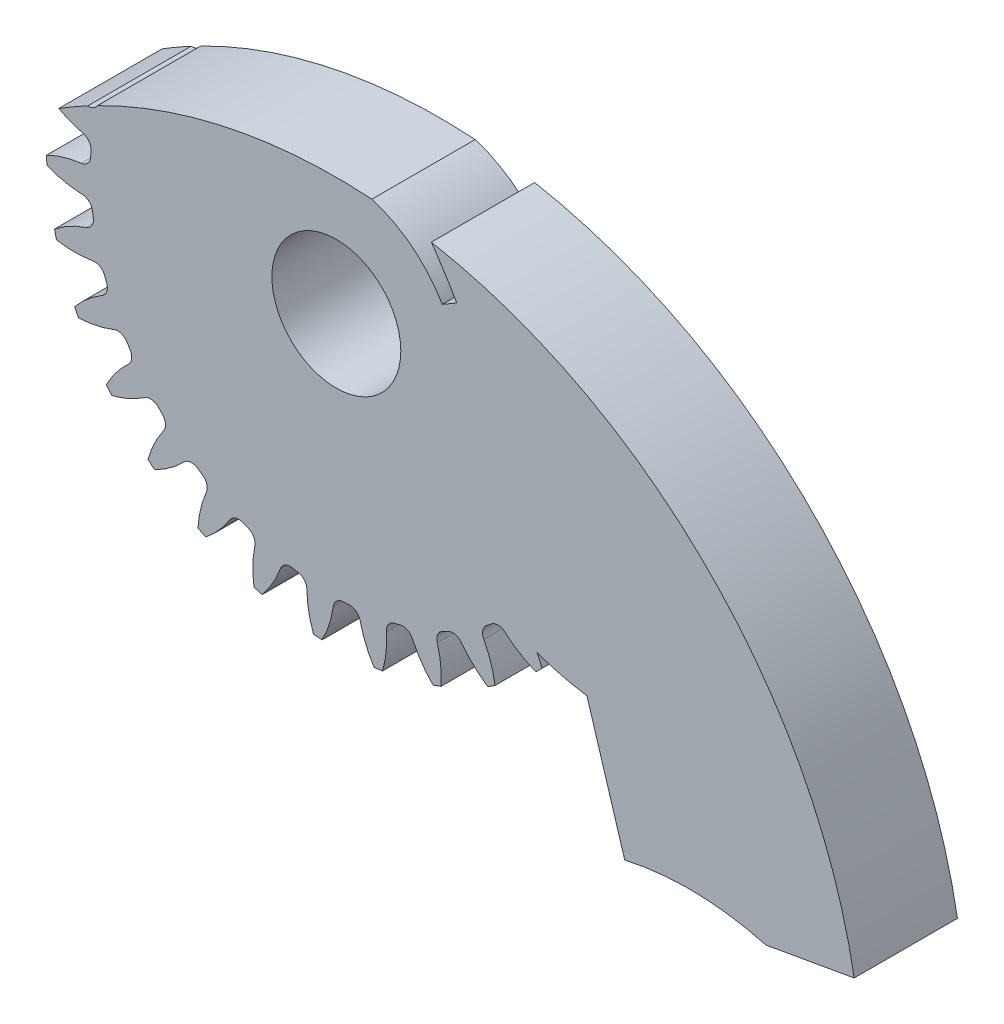
SolidWorks part; units mm, degrees
material "ABS"
ref_plane "Front" through (0, 0, 0) normal (0, 0, 1) x (1, 0, 0)
ref_plane "Top" through (0, 0, 0) normal (0, 1, 0) x (1, 0, 0)
ref_plane "Right" through (0, 0, 0) normal (1, 0, 0) x (0, 0, -1)
sketch "Sketch3" plane through (0, 0, 0) normal (0, 0, 1) x (1, 0, 0)
  circle A0 centre (0, 0) radius 40.64
  dimension "od" = 81.28
extrude "gearBody" add sketch "Sketch3" along normal blind 9.652
sketch "Sketch2" plane through (0, 0, 0) normal (0, 0, 1) x (1, 0, 0)
  line L0 (0, 0) -> (34.0786, 14.1158) construction
  line L1 (45.4751, -11.4855) -> (0, 0) construction
  line L2 (0, 0) -> (36.3143, 0) construction
  line L3 (38.0972, -0.458) -> (37.8451, -4.4001) construction
  line L5 (37.9712, -2.4291) -> (0, 0) construction
  line L7 (0, 0) -> (36.8864, 0) construction
  arc A0 (36.879, -0.7403) -> (36.6727, -3.9649) centre (0, 0) ccw construction
  arc A1 (40.637, 0.4947) -> (40.2427, -5.6687) centre (0, 0) ccw construction
  arc A2 (38.0972, -0.458) -> (37.8451, -4.4001) centre (0, 0) ccw construction
  arc A3 (34.9015, -2.6404) -> (34.9534, -1.8283) centre (0, 0) ccw
  arc A4 (45.4751, -11.4855) -> (35.6466, -3.6712) centre (32.0022, -18.3431) ccw
  arc A5 (45.4751, -11.4855) -> (46.5679, 5.5974) centre (0, 0) ccw
  arc A6 (46.5679, 5.5974) -> (35.8238, -0.9008) centre (34.0786, 14.1158) cw
  arc A7 (34.9534, -1.8283) -> (35.8238, -0.9008) centre (35.9376, -1.8798) cw
  arc A8 (35.6466, -3.6712) -> (34.9015, -2.6404) centre (35.8842, -2.7147) cw
  arc A9 (34.4461, -1.8018) -> (35.7652, -0.3962) centre (35.9376, -1.8798) cw
  arc A10 (46.8801, 7.0756) -> (35.7652, -0.3962) centre (34.0786, 14.1158) cw
  arc A11 (45.5964, -12.9914) -> (46.8801, 7.0756) centre (0, 0) ccw
  arc A12 (45.5964, -12.9914) -> (35.5241, -4.1642) centre (32.0022, -18.3431) ccw
  arc A13 (35.5241, -4.1642) -> (34.3949, -2.6021) centre (35.8842, -2.7147) cw
  arc A14 (34.3949, -2.6021) -> (34.4461, -1.8018) centre (0, 0) ccw
  point P6 (46.5679, 5.5974)
  point P22 (45.4751, -11.4855)
  dimension "D1" = 0.508
  dimension "baseDia" = 73.7729
  dimension "od" = 81.28
  dimension "pd" = 76.2
  dimension "rd" = 70.0024
  dimension "rFillet" = 0.9855
  dimension "pointX" = 46.5679
  dimension "pointY" = 5.5974
  dimension "CTT" = 3.9421
  dimension "flankCenterAngle" = 22.5
extrude "toothCut" cut sketch "Sketch2" along normal through all contours A8 A4 A5 A6 A7 A3 | A14 A13 A12 A11 A10 A9 A4 A8 A3 A7 A6 A5 region at (42.6325, -2.7272, 0) region at (35.023, -1.0214, 0)
pattern_circular "CirPattern1" count 30 over 360 about axis through (0, 0, 9.652) along (0, 0, -1) of "toothCut"
scale "Scale1" scale about centroid uniform scaling no x scale factor 0.666667 y scale factor 0.666667 z scale factor 1
sketch "hub1Dia" plane through (0, 0, 0) normal (0, 0, -1) x (-1, 0, 0)
  circle A0 centre (0, 0) radius 12.7
  dimension "hub1Dia" = 25.4
sketch "hub2Dia" plane through (0, 0, 9.652) normal (0, 0, 1) x (1, 0, 0)
  circle A0 centre (0, 0) radius 12.7
  dimension "hub2dia" = 25.4
sketch "boreDia" plane through (0, 0, 0) normal (0, 0, 1) x (1, 0, 0)
  circle A0 centre (0, 0) radius 6.0255
  dimension "boreDia" = 12.051
extrude "bore" cut sketch "boreDia" against normal mid plane 25400
sketch "Sketch4" plane through (0, 0, 9.652) normal (0, 0, 1) x (1, 0, 0)
  arc A0 (17.9437, -83.8564) -> (-17.9437, -83.8564) centre (0, -38.1) ccw
  arc A2 (-17.9437, -83.8564) -> (17.9437, -83.8564) centre (0, 0) cw
  point P1 (4.7613, -87.0178)
  point P2 (27.7548, 2.4622)
  point P6 (26.9247, 3.0179)
  point P9 (27.0842, 3.0179)
  point P10 (26.9247, 3.0179)
  point P11 (17.9437, -83.8564)
  dimension "D1" = 98.298
  dimension "D2" = 38.1
extrude "Cut-Extrude1" cut sketch "Sketch4" against normal through all contours A0 region at (0, 18.3935, 9.652)
sketch "Sketch5" plane through (0, 0, 9.652) normal (0, 0, 1) x (1, 0, 0)
  line L0 (0, -38.1) -> (49.53, -38.1) construction
  line L1 (0, 0) -> (0, -38.1) construction
  line L2 (0, -38.1) -> (-24.765, 4.7942) construction
  line L3 (0, -38.1) -> (42.8942, -62.865) construction
  line L4 (23.4248, -19.2156) -> (26.9592, -30.742)
  line L6 (48.7775, -29.4992) -> (0, -38.1) construction
  line L7 (40.1449, -31.0214) -> (48.7775, -29.4992)
  circle A0 centre (0, -38.1) radius 49.53 construction
  circle A2 centre (0, -38.1) radius 14.3933 construction
  circle A3 centre (32.9956, -57.15) radius 27.0891 construction
  arc A4 (26.9592, -30.742) -> (40.1449, -31.0214) centre (32.9956, -57.15) cw
  arc A5 (48.7775, -29.4992) -> (8.0038, 10.779) centre (0, -38.1) ccw
  arc A6 (24.6567, 4.8566) -> (-22.5513, 5.9983) centre (0, -38.1) ccw construction
  spline S0 degree 2 poles (8.0038, 10.779) (4.7007, -16.4877) (23.4248, -19.2156) knots 0 0 0 1 1 1
  point P16 (0, 0)
  point P20 (0, 0)
  dimension "D2" = 28.7867
  dimension "D4" = 54.1782
  dimension "D1" = 120
  dimension "D3" = 120
  dimension "D5" = 38.1
  dimension "D6" = 80
extrude "Boss-Extrude1" add sketch "Sketch5" against normal up to surface (9.652 mm away) up to face at (6.0255, 0, 0)
sketch "Sketch6" plane through (0, 0, 9.652) normal (0, 0, 1) x (1, 0, 0)
  line L0 (0, 0) -> (-32.9956, -19.05) construction
  line L1 (0, 0) -> (0, -38.1) construction
  line L2 (-32.9956, -19.05) -> (0, 0) construction
  line L3 (11.2625, 6.5024) -> (9.8987, 5.715)
  circle A0 centre (-32.9956, -19.05) radius 49.53 construction
  circle A1 centre (-32.9956, -19.05) radius 51.1048 construction
  arc A3 (48.7775, -29.4992) -> (8.0038, 10.779) centre (0, -38.1) ccw construction
  arc A4 (11.2625, 6.5024) -> (8.5694, 10.6831) centre (-32.9956, -19.05) ccw
  circle A5 centre (0, -38.1) radius 49.53 construction
  arc A6 (8.5694, 10.6831) -> (0, 11.43) centre (0, -38.1) ccw
  arc A7 (9.8987, 5.715) -> (0, 11.43) centre (0, 0) ccw
  dimension "D1" = 99.06
  dimension "D4" = 102.2096
  dimension "D2" = 60
  dimension "D3" = 38.1
extrude "Body Tube Cut Out" cut sketch "Sketch6" against normal through all
extrude "Cut-Extrude2" cut sketch "Sketch4<7>" against normal through all
sketch "Sketch4<7>" plane through (0, 0, 9.652) normal (0, 0, 1) x (1, 0, 0) same geometry as "Sketch4"
equation "\"Aft_Section_Length\" = 32in"
equation "\"Mid_Coupler_Length\" = 12in"
equation "\"AB_Coupler_OD_Length\"= 1in"
equation "\"AB_Coupling_Section_Length\"= 0.375in"
equation "\"AB_Coupler_Length\"= \"AB_Coupler_OD_Length\" + \"AB_Coupling_Section_Length\" * 2"
equation "\"Cutout_Angle\" = 60"
equation "\"AB_Paddle_Height\" = 0.375in"
equation "\"AB_Coupler_Num_Screws\"= 4"
equation "\"Num_Cutouts\" = 4"
equation "\"AB_Coupler_OD\"= 4.024in"
equation "\"AB_Coupler_ID\"= 3.7in"
equation "\"AB_Coupler_Surface_Diameter\"= 3.899in"
equation "\"AB_Coupling_Screw_Diameter\"= 0.1065in"
equation "\"AB_Central_Bushing_Length\" = 0.75in"
equation "\"Lead_Screw_Dist\" = 2in"
equation "\"Lead_Screw_Diam\" = 0.375in"
equation "\"Lead_Screw_Length\" = \"Mid_Coupler_Length\" + 2*0.375in + 2*0.5in"
equation "\"Paddle_Pin_Offset\" = 0.25in"
equation "\"Paddle_Pin_Radius\" = 2.25*2/3in"
equation "\"Fwd_BKHD_From_Top\" = 18in"
equation "\"D1@Sketch4\"=\"Body_Tube_ID\"-0.03"
equation "\"D2@Sketch4\"=\"Paddle_Pin_Radius\""
equation "\"Motor_OD\" = 54.4mm"
equation "\"Paddle_Gear_OD\" = 3.2in"
equation "\"Drive_Gear_OD\" = 1.7*2/3in"
equation "\"Fin_Thickness\" = 0.118in"
equation "\"DB9_Hole_Dist\" = 25mm"
equation "\"Motor_Length\" = 401mm"
equation "\"Body_Tube_OD\"= 4.024in"
equation "\"Body_Tube_ID\"= 3.90in"
equation "\"Coupler_OD\" = 3.899in"
equation "\"Coupler_ID\" = 3.755in"
equation "\"Fwd_Section_Length\" = 20in"
equation "\"Mid_Section_Length\" = 4in"
equation "\"Aft_Upper_Tube_Length\" = 10in"
equation "\"Aft_Lower_Tube_Length\" = 18in"
equation "\"Nosecone_Coupler_Length\" = 5in"
equation "\"Avionics_Bulkhead_Thickness\" = 0.25in"
equation "\"Avionics_Bulkhead_Lip\" = 0.125in"
equation "\"Avionics_Board_Length\" = \"Mid_Coupler_Length\" - 2*\"Avionics_Bulkhead_Lip\""
equation "\"Lead_Screw_Hole_Diam\" = 0.386in"
equation "\"Centering_Ring_Cutout_Dia\"=1.5in"
equation "\"Airbrakes_Wire_Hole_Dist\" = 1.1*2/3in"
equation "\"Airbrakes_Wire_Hole_Dia\" = 0.25in"
equation "\"DB9_Relief_Width\" = 0.47in"
equation "\"DB9_Relief_Hole_Offset\" = 0.09in"
equation "\"Servo_Gear_Offset\" = 0.5in"
equation "\"D2@Sketch5\"=\"Drive_Gear_OD\""
equation "\"D5@Sketch5\"=\"Paddle_Pin_Radius\""
equation "\"D1@Sketch6\"=\"Body_Tube_ID\""
equation "\"D2@Sketch6\"=60"
equation "\"D3@Sketch6\"=\"Paddle_Pin_Radius\""
equation "\"D4@Sketch6\"=\"Body_Tube_OD\""
equation "\"Airbrake_Shaft_Diameter\"= 12.051mm"
equation "\"boreDia@boreDia\"=\"Airbrake_Shaft_Diameter\""
